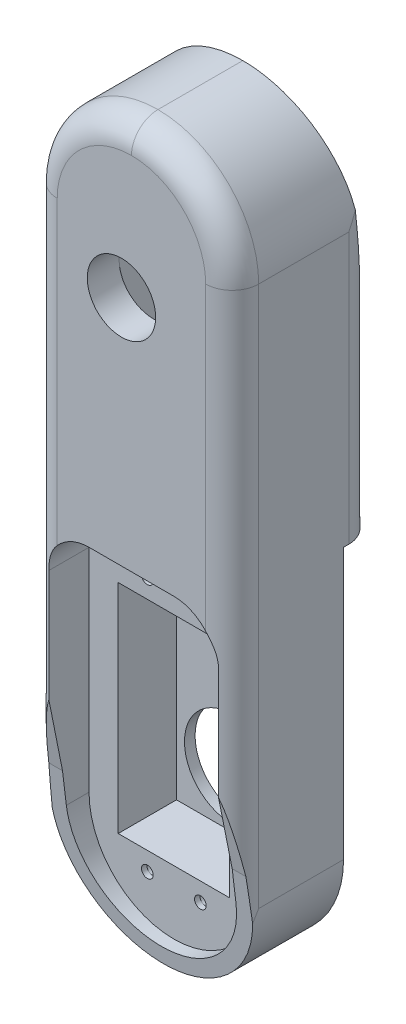
SolidWorks part; units mm, degrees
ref_plane "Front Plane" through (0, 0, 0) normal (0, 0, 1) x (1, 0, 0)
ref_plane "Top Plane" through (0, 0, 0) normal (0, 1, 0) x (1, 0, 0)
ref_plane "Right Plane" through (0, 0, 0) normal (1, 0, 0) x (0, 0, -1)
sketch "Sketch1" plane through (0, 0, 0) normal (0, 0, 1) x (1, 0, 0)
  line L5 (-19, -60) -> (19, -60)
  line L6 (-19, -60) -> (-19, 60)
  line L7 (-19, 60) -> (19, 60)
  line L8 (19, -60) -> (19, 60)
  line L9 (-19, -60) -> (19, 60) construction
  line L10 (-19, 60) -> (19, -60) construction
  line L11 (-10.5, -45) -> (10.5, -45)
  line L12 (-10.5, -45) -> (-10.5, -4)
  line L13 (-10.5, -4) -> (10.5, -4)
  line L14 (10.5, -45) -> (10.5, -4)
  line L15 (-10.5, -45) -> (10.5, -4) construction
  line L16 (-10.5, -4) -> (10.5, -45) construction
  point P0 (0, 0)
  point P6 (0, -24.5)
  dimension "D1" = 21
  dimension "D2" = 41
  dimension "D3" = 8.5
  dimension "D4" = 120
  dimension "D5" = 15
extrude "Boss-Extrude1" add sketch "Sketch1" along normal blind 11
ref_plane "Plane1" through (0, 0, 10) normal (0, 0, 1) x (1, 0, 0)
sketch "Sketch3" plane through (0, 0, 10) normal (0, 0, 1) x (1, 0, 0)
  line L0 (10.5, -4) -> (-10.5, -4) construction
  circle A0 centre (-5, -0.5) radius 1.3
  circle A1 centre (5, -0.5) radius 1.3
  circle A2 centre (5, -48.5) radius 1.3
  circle A3 centre (-5, -48.5) radius 1.3
  dimension "D1" = 2.6
  dimension "D2" = 5
  dimension "D3" = 3.5
  dimension "D4" = 2
  dimension "D5" = 2
extrude "Cut-Extrude1" cut sketch "Sketch3" against normal blind 8
fillet "Fillet3" radius 19 2 edges at (19, -60, 5.5) (-19, -60, 5.5)
sketch "Sketch4" plane through (0, 0, 11) normal (0, 0, 1) x (1, 0, 0)
  line L0 (16, -41) -> (16, 57)
  line L1 (16, 57) -> (-16, 57)
  line L2 (-16, 57) -> (-16, -41)
  line L3 (19, -41) -> (19, 60)
  line L4 (19, 60) -> (-19, 60)
  line L5 (-19, 60) -> (-19, -41)
  line L6 (19, -41) -> (19, 60)
  line L7 (19, 60) -> (-19, 60)
  line L8 (-19, 60) -> (-19, -41)
  arc A0 (-16, -41) -> (0, -57) centre (0, -41) ccw
  arc A1 (0, -57) -> (16, -41) centre (0, -41) ccw
  arc A2 (-19, -41) -> (0, -60) centre (0, -41) ccw
  arc A3 (0, -60) -> (19, -41) centre (0, -41) ccw
  arc A4 (-19, -41) -> (0, -60) centre (0, -41) ccw
  arc A5 (0, -60) -> (19, -41) centre (0, -41) ccw
  dimension "D1" = 0
  dimension "D2" = 3
extrude "Boss-Extrude2" add sketch "Sketch4" along normal blind 8
sketch "Sketch6" plane through (0, 0, 0) normal (1, 0, 0) x (0, 0, -1)
  line L7 (-13, -60) -> (-16, -35)
  line L8 (-16, -35) -> (-19, -20)
  line L9 (-19, -41) -> (-19, 60) construction
  line L10 (-19, -20) -> (-19, -60)
  line L11 (-19, -41) -> (-19, -60) construction
  line L12 (-19, -60) -> (-13, -60)
  line L13 (-11, -60) -> (0, -60) construction
  dimension "D1" = 6
  dimension "D2" = 25
  dimension "D3" = 15
  dimension "D4" = 3
extrude "Cut-Extrude2" cut sketch "Sketch6" against normal through all both and the other way through all
sketch "Sketch7" plane through (0, 0, 11) normal (0, 0, 1) x (1, 0, 0)
  line L0 (16, -20) -> (16, 57) construction
  line L1 (16, 7) -> (-16, 7)
  line L2 (16, 7) -> (16, 57)
  line L3 (16, 57) -> (-16, 57)
  line L4 (-16, 7) -> (-16, 57)
  dimension "D1" = 50
extrude "Boss-Extrude4" add sketch "Sketch7" along normal up to surface (8 mm away) up to face at (0, 19.25, 19)
sketch "Sketch8" plane through (0, 0, 0) normal (0, 0, -1) x (-1, 0, 0)
  line L0 (-19, 60) -> (19, 60)
  line L1 (19, 60) -> (19, -3.3108)
  line L2 (19, 60) -> (19, -41) construction
  line L3 (-19, 60) -> (-19, -4)
  line L4 (-19, -41) -> (-19, 60) construction
  line L7 (19, 10) -> (-19, 10)
  arc A0 (19, -3.3108) -> (-19, -4) centre (0.25, -17.4388) ccw
  line M2 (-19, 60) -> (-19, -41)
  line M6 (19, 60) -> (-19, 60)
  dimension "D1" = 23.4769
  dimension "D2" = 64
  dimension "D3" = 19.25
  dimension "D4" = 50
extrude "Boss-Extrude5" add sketch "Sketch8" along normal blind 8 contours L7 L1 M6 M2 region at (0, 35, 0)
sketch "Sketch27" plane through (0, 0, 0) normal (0, 0, -1) x (-1, 0, 0)
  line L0 (10.5, -45) -> (-10.5, -45) construction
  line L3 (19, -41) -> (19, 10)
  line L4 (19, 10) -> (-19, 10)
  line L5 (-19, 10) -> (-19, -41)
  line L6 (19, -41) -> (19, 10)
  line L7 (19, 10) -> (-19, 10)
  line L8 (-19, 10) -> (-19, -41)
  circle A0 centre (0, -34.75) radius 9
  arc A2 (-19, -41) -> (0, -60) centre (0, -41) ccw
  arc A3 (0, -60) -> (19, -41) centre (0, -41) ccw
  arc A4 (-19, -41) -> (0, -60) centre (0, -41) ccw
  arc A5 (0, -60) -> (19, -41) centre (0, -41) ccw
  dimension "D2" = 18
  dimension "D3" = 10.25
  dimension "D1" = 0
extrude "Boss-Extrude10" add sketch "Sketch27" along normal blind 2
sketch "Sketch28" plane through (0, 60, 0) normal (0, 1, 0) x (1, 0, 0)
  line L4 (19, -19) -> (19, 8)
  line L5 (19, 8) -> (-19, 8)
  line L6 (-19, 8) -> (-19, -19)
  line L7 (-19, -19) -> (19, -19)
  line L8 (19, -19) -> (19, 8)
  line L9 (19, 8) -> (-19, 8)
  line L10 (-19, 8) -> (-19, -19)
  line L11 (-19, -19) -> (19, -19)
  dimension "D1" = 0
extrude "Boss-Extrude11" add sketch "Sketch28" along normal blind 20
fillet "Fillet4" radius 19 2 edges at (-19, 80, 5.5) (19, 80, 5.5)
sketch "Sketch29" plane through (0, 0, -8) normal (0, 0, -1) x (-1, 0, 0)
  line L6 (16, 13) -> (16, 61)
  line L7 (-16, 61) -> (-16, 13)
  line L8 (-16, 13) -> (16, 13)
  line L9 (16, 13) -> (16, 61)
  line L10 (-16, 61) -> (-16, 13)
  line L11 (-16, 13) -> (16, 13)
  arc A4 (16, 61) -> (0, 77) centre (0, 61) ccw
  arc A5 (0, 77) -> (-16, 61) centre (0, 61) ccw
  arc A6 (16, 61) -> (0, 77) centre (0, 61) ccw
  arc A7 (0, 77) -> (-16, 61) centre (0, 61) ccw
  dimension "D1" = 3
extrude "Cut-Extrude14" cut sketch "Sketch29" against normal blind 8
sketch "Sketch30" plane through (0, 0, 0) normal (0, 0, -1) x (-1, 0, 0)
  line L0 (-16, 13) -> (16, 13) construction
  line L1 (-4.6176, 34.5) -> (8.3824, 34.5)
  line L2 (-4.6176, 34.5) -> (-4.6176, 57.5)
  line L3 (-4.6176, 57.5) -> (8.3824, 57.5)
  line L4 (8.3824, 34.5) -> (8.3824, 57.5)
  line L5 (-4.6176, 34.5) -> (8.3824, 57.5) construction
  line L6 (-4.6176, 57.5) -> (8.3824, 34.5) construction
  point P0 (1.8824, 46)
  dimension "D3" = 11.5
  dimension "D1" = 13
  dimension "D2" = 21.5
  dimension "D4" = 23
sketch "Sketch32" plane through (0, 0, 19) normal (0, 0, 1) x (1, 0, 0)
  line L0 (-19, 12) -> (19, 12)
  line L7 (-19, 61) -> (-19, -20)
  line L8 (-19, -20) -> (-16, -20)
  line L9 (-16, -20) -> (-16, 7)
  line L10 (-16, 7) -> (16, 7)
  line L11 (16, 7) -> (16, -20)
  line L12 (16, -20) -> (19, -20)
  line L13 (19, -20) -> (19, 61)
  line L14 (-19, 61) -> (-19, -20)
  line L15 (-19, -20) -> (-16, -20)
  line L16 (-16, -20) -> (-16, 7)
  line L17 (-16, 7) -> (16, 7)
  line L18 (16, 7) -> (16, -20)
  line L19 (16, -20) -> (19, -20)
  line L20 (19, -20) -> (19, 61)
  arc A2 (19, 61) -> (0, 80) centre (0, 61) ccw
  arc A3 (0, 80) -> (-19, 61) centre (0, 61) ccw
  arc A4 (19, 61) -> (0, 80) centre (0, 61) ccw
  arc A5 (0, 80) -> (-19, 61) centre (0, 61) ccw
  dimension "D2" = 5
  dimension "D1" = 0
sketch "Sketch33" plane through (19, 0, 0) normal (1, 0, 0) x (0, 0, -1)
  line L0 (2, 80) -> (8, 40)
  line L1 (-13, 80) -> (8, 80) construction
  line L2 (8, 61) -> (8, 10) construction
  line L3 (2, 80) -> (8, 80)
  line L4 (8, 80) -> (8, 40)
  dimension "D1" = 6
  dimension "D2" = 40
extrude "Cut-Extrude18" cut sketch "Sketch33" against normal through all
fillet "Fillet7" radius 5 6 edges at (-19, 25, -8) (19, 25, -8) (-19, 20.5, 19) (19, 20.5, 19) (-13.435, 74.435, 19) (13.435, 74.435, 19)
sketch "Sketch35" plane through (0, 0, 11) normal (0, 0, 1) x (1, 0, 0)
  line L0 (10.5, -4) -> (-10.5, -4) construction
  line L1 (0, 0) -> (0, -6.946) construction
  circle A0 centre (-5, -0.5) radius 1.1
  circle A1 centre (5, -0.5) radius 1.1
  circle A2 centre (5, -48.5) radius 1.1
  circle A3 centre (-5, -48.5) radius 1.1
  dimension "D1" = 2.2
  dimension "D2" = 5
  dimension "D3" = 3.5
  dimension "D4" = 2
  dimension "D5" = 2
extrude "Cut-Extrude20" cut sketch "Sketch35" against normal blind 8
fillet "Fillet8" radius 8 4 edges at (-16, 7, 14.7913) (16, 7, 14.7913) (16, 13, -3.7913) (-16, 13, -3.7913)
sketch "Sketch36" plane through (0, 0, 0) normal (0, 0, -1) x (-1, 0, 0)
  circle A0 centre (1.8824, 50.8321) radius 6.45
  dimension "D1" = 12.9
extrude "Cut-Extrude21" cut sketch "Sketch36" against normal through all
extrude "Cut-Extrude22" cut sketch "Sketch30" against normal blind 13
